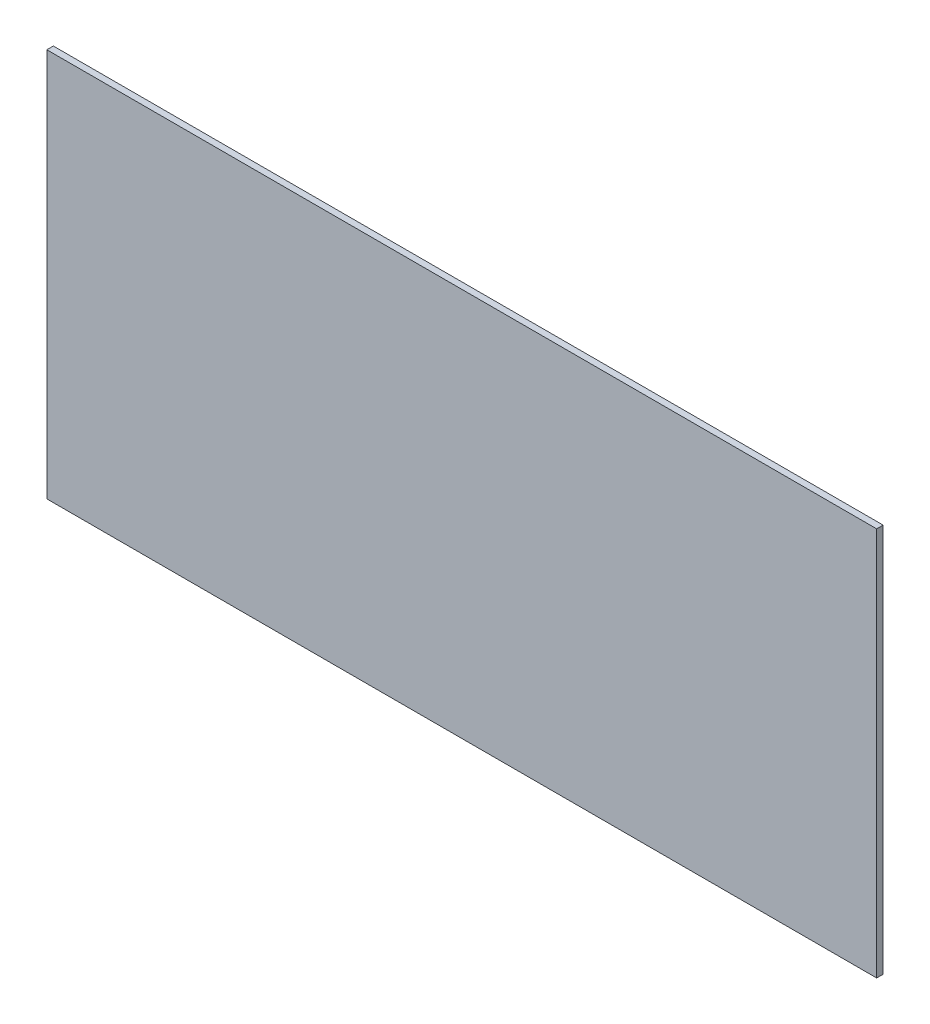
SolidWorks part; units mm, degrees
ref_plane "Front Plane" through (0, 0, 0) normal (0, 0, 1) x (1, 0, 0)
ref_plane "Top Plane" through (0, 0, 0) normal (0, 1, 0) x (1, 0, 0)
ref_plane "Right Plane" through (0, 0, 0) normal (1, 0, 0) x (0, 0, -1)
sketch "Sketch1" plane through (0, 0, 0) normal (0, 0, 1) x (1, 0, 0)
  line L1 (0, 0) -> (406.4, 0)
  line L2 (0, 0) -> (0, 190.5)
  line L3 (0, 190.5) -> (406.4, 190.5)
  line L4 (406.4, 0) -> (406.4, 190.5)
  dimension "D1" = 190.5
  dimension "D2" = 406.4
extrude "Boss-Extrude1" add sketch "Sketch1" along normal blind 3.175
